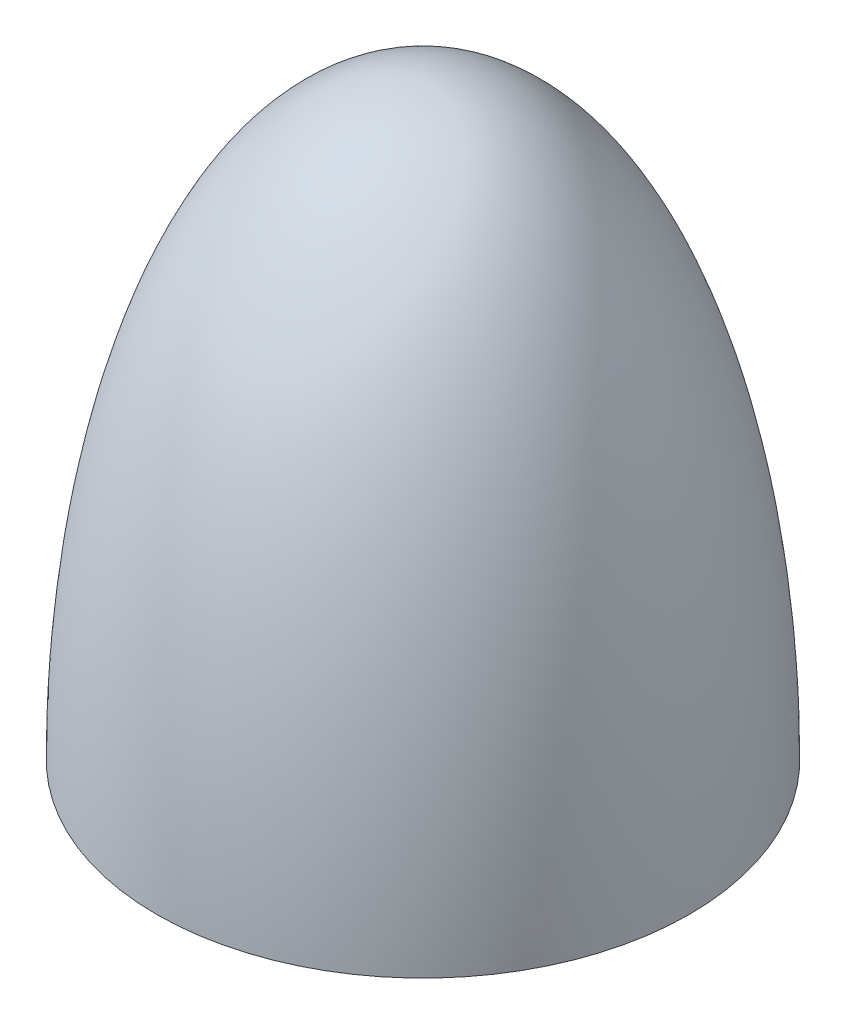
SolidWorks part; units mm, degrees
ref_plane "Front Plane" through (0, 0, 0) normal (0, 0, 1) x (1, 0, 0)
ref_plane "Top Plane" through (0, 0, 0) normal (0, 1, 0) x (1, 0, 0)
ref_plane "Right Plane" through (0, 0, 0) normal (1, 0, 0) x (0, 0, -1)
sketch "Sketch1" plane through (0, 0, 0) normal (0, 0, 1) x (1, 0, 0)
  line L0 (0, 20) -> (0, 22)
  line L1 (8, 0) -> (10, 0)
  ellipse E0 centre (0, 0) end of major axis (0, 20) minor radius 8 (8, 0) -> (0, 20) ccw
  spline S1 degree 3 poles (10, 0) (10, 0.6807) (9.9465, 3.4034) (9.4118, 8.7546) (8.01, 14.0395) (6.2099, 17.7501) (4.5638, 19.9723) (2.5359, 21.5619) (0.8453, 22) (0, 22) knots 4.712389 4.712389 4.712389 4.712389 4.810564 5.105088 5.497787 5.694137 5.890486 6.086836 6.283185 6.283185 6.283185 6.283185
  dimension "D1" = 8
  dimension "D2" = 20
ref_axis "Axis1" through (0, 20, 0) along (0, 1, 0)
revolve "Revolve1" add sketch "Sketch1" angle 360 about L0
